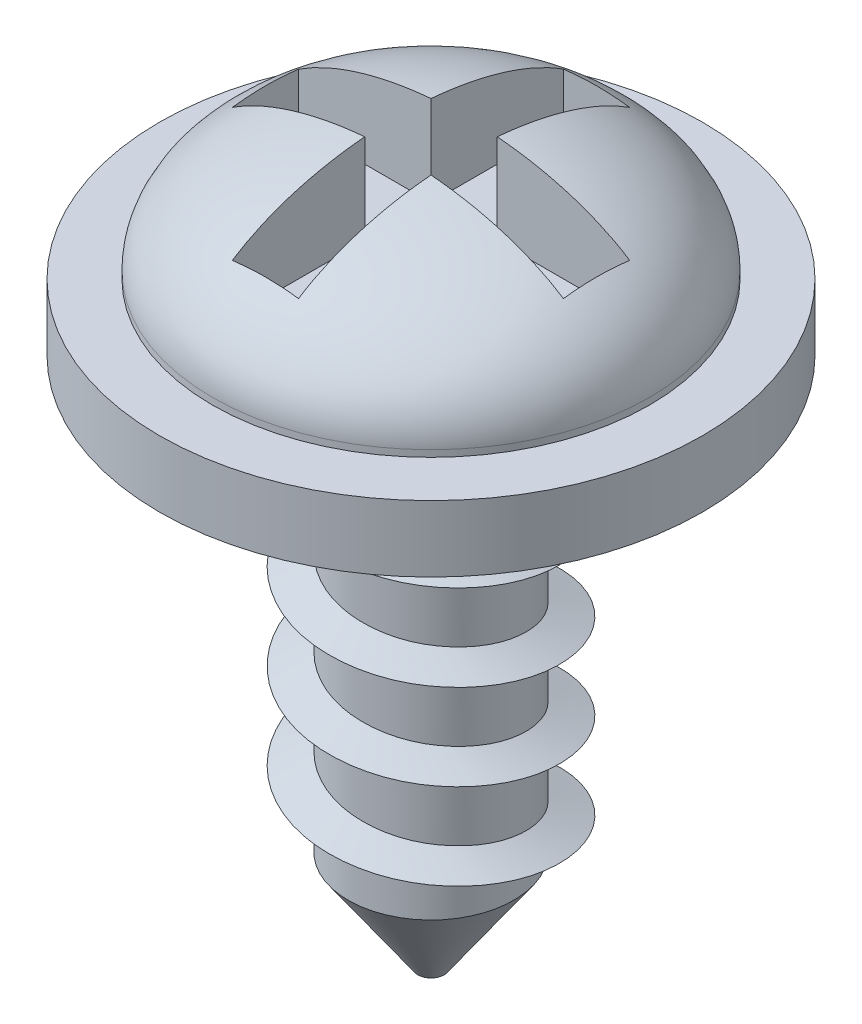
SolidWorks part; units mm, degrees
ref_plane "Front Plane" through (0, 0, 0) normal (0, 0, 1) x (1, 0, 0)
ref_plane "Top Plane" through (0, 0, 0) normal (0, 1, 0) x (1, 0, 0)
ref_plane "Right Plane" through (0, 0, 0) normal (1, 0, 0) x (0, 0, -1)
sketch "Sketch1" plane through (0, 0, 0) normal (0, 1, 0) x (1, 0, 0)
  circle A0 centre (0, 0) radius 4.1
  dimension "D1" = 8.2
extrude "Boss-Extrude1" add sketch "Sketch1" along normal blind 1
sketch "Sketch2" plane through (0, 1, 0) normal (0, 1, 0) x (1, 0, 0)
  circle A0 centre (0, 0) radius 3.3
  dimension "D1" = 6.6
extrude "Boss-Extrude2" add sketch "Sketch2" along normal blind 0.1
dome "Dome1" faces to dome 1 distance 1.8 reverse direction no elliptical dome yes face at (0, 1.1, 3.3) parameters "D1"=1.8
ref_plane "Plane1" through (0, 5, 0) normal (0, 1, 0) x (-1, 0, 0)
sketch "Sketch3" plane through (0, 5, 0) normal (0, 1, 0) x (-1, 0, 0)
  line L0 (1.595, 0) -> (-1.595, 0) construction
  line L1 (-0.5, 2.5) -> (0.5, 2.5)
  line L2 (-0.5, 2.5) -> (-0.5, 0.5)
  line L3 (-0.5, -2.5) -> (0.5, -2.5)
  line L4 (0.5, 2.5) -> (0.5, 0.5)
  line L5 (-2.5, 0.5) -> (-0.5, 0.5)
  line L6 (-2.5, 0.5) -> (-2.5, -0.5)
  line L7 (-2.5, -0.5) -> (-0.5, -0.5)
  line L8 (2.5, 0.5) -> (2.5, -0.5)
  line L9 (0, 1.595) -> (0, -1.595) construction
  line L10 (0.5, 0.5) -> (2.5, 0.5)
  line L11 (-0.5, -0.5) -> (-0.5, -2.5)
  line L12 (0.5, -0.5) -> (2.5, -0.5)
  line L13 (0.5, -0.5) -> (0.5, -2.5)
  dimension "D1" = 1
  dimension "D2" = 1
  dimension "D3" = 0.5
  dimension "D4" = 0.5
  dimension "D5" = 5
  dimension "D6" = 2.5
  dimension "D7" = 5
  dimension "D8" = 2.5
extrude "Cut-Extrude1" cut sketch "Sketch3" against normal blind 3.5
sketch "Sketch4" plane through (0, 0, 0) normal (0, -1, 0) x (1, 0, 0)
  circle A0 centre (0, 0) radius 1.25
  dimension "D1" = 2.5
extrude "Boss-Extrude3" add sketch "Sketch4" along normal blind 8
chamfer "Chamfer1" distance 1.5 angle 35 1 edges at (0, -8, -1.25) first distance on face at (0, -8, -1.25)
sketch "Sketch5" plane through (0, 0, 0) normal (0, -1, 0) x (1, 0, 0)
  circle A0 centre (0, 0) radius 1.25
curve "Helix/Spiral1" pitch 1.3 height 6.5 radius 1.25 left hand yes centre (0, 0, 0) axis (0, -1, 0) start towards (0, 0, -1)
sketch "Sketch6" plane through (0, 0, 0) normal (0, 0, 1) x (1, 0, 0)
  line L0 (-1.75, 0) -> (-1.0478, 0.2556)
  line L1 (4.51, 0) -> (-4.51, 0) construction
  line L2 (-1.0478, 0.2556) -> (-1.0478, -0.2556)
  line L3 (-1.0478, -0.2556) -> (-1.75, 0)
  line L4 (-1.25, 0) -> (-1.25, -6.5) construction
  dimension "D1" = 20
  dimension "D2" = 40
  dimension "D3" = 0.5
sweep "Sweep1" add profiles "Sketch6" path "Helix/Spiral1"
